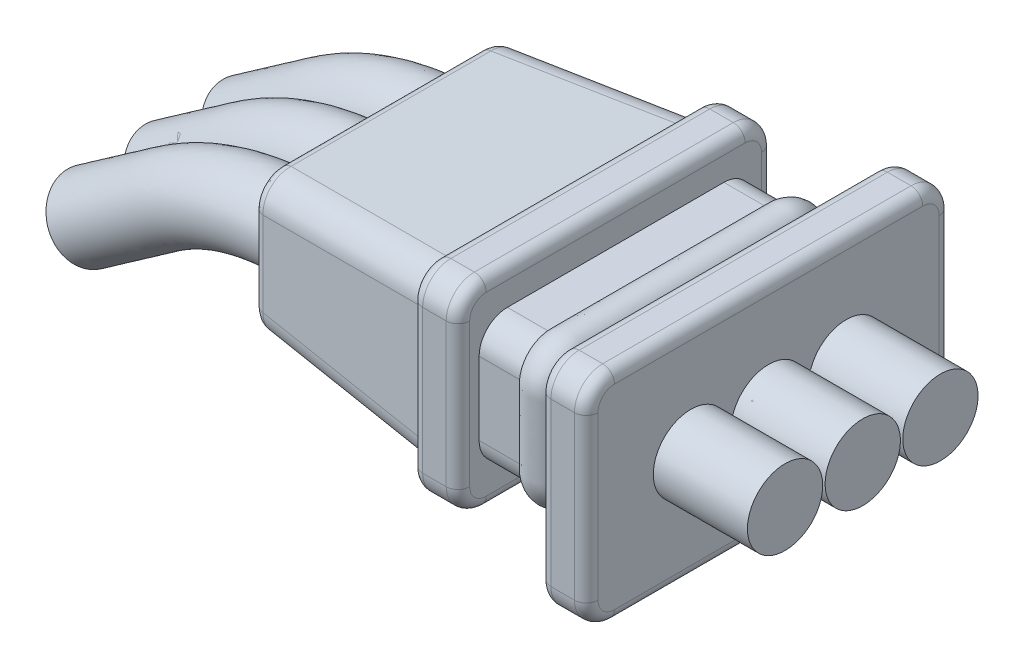
SolidWorks part; units mm, degrees
material "Rubber"
ref_plane "Front Plane" through (0, 0, 0) normal (0, 0, 1) x (1, 0, 0)
ref_plane "Top Plane" through (0, 0, 0) normal (0, 1, 0) x (1, 0, 0)
ref_plane "Right Plane" through (0, 0, 0) normal (1, 0, 0) x (0, 0, -1)
sketch "Sketch1" plane through (0, 0, 0) normal (1, 0, 0) x (0, 0, -1)
  line L1 (-3.875, 2.325) -> (3.875, 2.325)
  line L2 (-3.875, 2.325) -> (-3.875, -2.325)
  line L3 (-3.875, -2.325) -> (3.875, -2.325)
  line L4 (3.875, 2.325) -> (3.875, -2.325)
  line L5 (-3.875, 2.325) -> (3.875, -2.325) construction
  line L6 (-3.875, -2.325) -> (3.875, 2.325) construction
  point P0 (0, 0)
  dimension "D1" = 7.75
  dimension "D2" = 4.65
extrude "Boss-Extrude1" add sketch "Sketch1" along normal blind 1
sketch "Sketch2" plane through (0, 0, 0) normal (-1, 0, 0) x (0, 0, 1)
  line L1 (2.9, -1.375) -> (-2.9, -1.375)
  line L2 (2.9, -1.375) -> (2.9, 1.375)
  line L3 (2.9, 1.375) -> (-2.9, 1.375)
  line L4 (-2.9, -1.375) -> (-2.9, 1.375)
  line L5 (2.9, -1.375) -> (-2.9, 1.375) construction
  line L6 (2.9, 1.375) -> (-2.9, -1.375) construction
  point P0 (0, 0)
  dimension "D1" = 5.8
  dimension "D2" = 2.75
extrude "Boss-Extrude2" add sketch "Sketch2" along normal blind 2.25
sketch "Sketch3" plane through (-2.25, 0, 0) normal (-1, 0, 0) x (0, 0, 1)
  line L1 (3.35, -2.125) -> (-3.35, -2.125)
  line L2 (3.35, -2.125) -> (3.35, 2.125)
  line L3 (3.35, 2.125) -> (-3.35, 2.125)
  line L4 (-3.35, -2.125) -> (-3.35, 2.125)
  line L5 (3.35, -2.125) -> (-3.35, 2.125) construction
  line L6 (3.35, 2.125) -> (-3.35, -2.125) construction
  point P0 (0, 0)
  dimension "D1" = 6.7
  dimension "D2" = 4.25
extrude "Boss-Extrude3" add sketch "Sketch3" along normal blind 1
sketch "Sketch4" plane through (-3.25, 0, 0) normal (-1, 0, 0) x (0, 0, 1)
  line L1 (3.05, -1.825) -> (-3.05, -1.825)
  line L2 (3.05, -1.825) -> (3.05, 1.825)
  line L3 (3.05, 1.825) -> (-3.05, 1.825)
  line L4 (-3.05, -1.825) -> (-3.05, 1.825)
  line L5 (3.05, -1.825) -> (-3.05, 1.825) construction
  line L6 (3.05, 1.825) -> (-3.05, -1.825) construction
  point P0 (0, 0)
  dimension "D1" = 6.1
  dimension "D2" = 3.65
extrude "Boss-Extrude4" add sketch "Sketch4" along normal blind 4 draft 5
fillet "Fillet1" radius 0.6 16 edges at (-1.125, -1.375, -2.9) (-1.125, 1.375, -2.9) (-1.125, -1.375, 2.9) (0.5, 2.325, -3.875) (0.5, -2.325, -3.875) (0.5, -2.325, 3.875) (-2.75, 2.125, -3.35) (-2.75, -2.125, -3.35) (-5.25, -1.65, -2.875) (-5.25, -1.65, 2.875) (-5.25, 1.65, -2.875) (-2.75, -2.125, 3.35) (0.5, 2.325, 3.875) (-1.125, 1.375, 2.9) (-5.25, 1.65, 2.875) (-2.75, 2.125, 3.35)
sketch "Sketch7" plane through (0, 0, 0) normal (-1, 0, 0) x (0, 0, 1)
  line L0 (-2.3, -1.375) -> (2.3, -1.375) construction
  line L1 (-2.9, 0.775) -> (-2.9, -0.775) construction
  line L2 (2.9, -0.775) -> (2.9, 0.775) construction
  line L3 (2.3, 1.375) -> (-2.3, 1.375) construction
  line L4 (-2.3, -1.375) -> (2.3, -1.375)
  line L5 (-2.9, 0.775) -> (-2.9, -0.775)
  line L6 (2.9, -0.775) -> (2.9, 0.775)
  line L7 (2.3, 1.375) -> (-2.3, 1.375)
  arc A0 (-2.9, -0.775) -> (-2.3, -1.375) centre (-2.3, -0.775) ccw construction
  arc A1 (-2.3, 1.375) -> (-2.9, 0.775) centre (-2.3, 0.775) ccw construction
  arc A2 (2.3, -1.375) -> (2.9, -0.775) centre (2.3, -0.775) ccw construction
  arc A3 (2.9, 0.775) -> (2.3, 1.375) centre (2.3, 0.775) ccw construction
  arc A4 (-2.9, -0.775) -> (-2.3, -1.375) centre (-2.3, -0.775) ccw
  arc A5 (-2.3, 1.375) -> (-2.9, 0.775) centre (-2.3, 0.775) ccw
  arc A6 (2.3, -1.375) -> (2.9, -0.775) centre (2.3, -0.775) ccw
  arc A7 (2.9, 0.775) -> (2.3, 1.375) centre (2.3, 0.775) ccw
sketch "Sketch5" plane through (0, 0, 0) normal (0, 1, 0) x (1, 0, 0)
  line L1 (-0.625, 2.9) -> (-1, 2.6835) construction
  line L3 (-1, 2.6835) -> (-1.375, 2.9) construction
  line L5 (-2.25, 2.9) -> (0, 2.9) construction
  line L6 (-2.25, -2.75) -> (-2.25, 2.75) construction
  line L7 (-0.625, 2.9) -> (-1.375, 2.9)
  arc A0 (-1.375, 2.9) -> (-0.625, 2.9) centre (-1, 2.6835) cw
  dimension "D1" = 0.75
  dimension "D2" = 0.875
  dimension "D3" = 120
sweep "Sweep2" add profiles "Sketch5" path "Sketch7"
fillet "Fillet2" radius 0.25 40 edges at (1, -2.1493, 3.6993) (1, 0, 3.875) (1, 2.1493, 3.6993) (1, 2.325, 0) (1, 2.1493, -3.6993) (1, 0, -3.875) (1, -2.1493, -3.6993) (0, -2.1493, 3.6993) (0, 0, 3.875) (0, 2.1493, 3.6993) (0, 2.325, 0) (0, 2.1493, -3.6993) (0, 0, -3.875) (0, -2.1493, -3.6993) (1, -2.325, 0) (0, -2.325, 0) (-7.25, -1.3003, -2.5253) (-7.25, 0, -2.7) (-7.25, 1.3003, -2.5253) (-7.25, 1.475, 0) (-7.25, 1.3003, 2.5253) (-7.25, 0, 2.7) (-7.25, -1.3003, 2.5253) (-3.25, -1.9493, -3.1743) (-3.25, 0, -3.35) (-3.25, 1.9493, -3.1743) (-3.25, 2.125, 0) (-3.25, 1.9493, 3.1743) (-3.25, 0, 3.35) (-3.25, -1.9493, 3.1743) (-2.25, -1.9493, -3.1743) (-2.25, 0, -3.35) (-2.25, 1.9493, -3.1743) (-2.25, 2.125, 0) (-2.25, 1.9493, 3.1743) (-2.25, 0, 3.35) (-2.25, -1.9493, 3.1743) (-7.25, -1.475, 0) (-3.25, -2.125, 0) (-2.25, -2.125, 0)
sketch "Sketch15" plane through (-7.25, 0, 0) normal (-1, 0, 0) x (0, 0, 1)
  line L0 (0, 0) -> (1.65, 0) construction
  line L1 (0, 0) -> (-1.65, 0) construction
  line L2 (-0.8547, 0.25) -> (-0.7953, 0.25)
  line L3 (-0.8547, -0.25) -> (-0.7953, -0.25)
  line L4 (0.7953, -0.25) -> (0.8547, -0.25)
  line L5 (0.7953, 0.25) -> (0.8547, 0.25)
  arc A0 (0.7485, 0.2824) -> (-0.7485, 0.2824) centre (0, 0) ccw
  arc A1 (0.9015, -0.2824) -> (0.9015, 0.2824) centre (1.65, 0) ccw
  arc A2 (-0.9015, 0.2824) -> (-0.9015, -0.2824) centre (-1.65, 0) ccw
  arc A3 (-0.7485, -0.2824) -> (0.7485, -0.2824) centre (0, 0) ccw
  arc A4 (0.8547, -0.25) -> (0.9015, -0.2824) centre (0.8547, -0.3) cw
  arc A5 (0.7485, -0.2824) -> (0.7953, -0.25) centre (0.7953, -0.3) cw
  arc A6 (0.7485, 0.2824) -> (0.7953, 0.25) centre (0.7953, 0.3) ccw
  arc A7 (0.8547, 0.25) -> (0.9015, 0.2824) centre (0.8547, 0.3) ccw
  arc A8 (-0.7953, -0.25) -> (-0.7485, -0.2824) centre (-0.7953, -0.3) cw
  arc A9 (-0.8547, -0.25) -> (-0.9015, -0.2824) centre (-0.8547, -0.3) ccw
  arc A10 (-0.7953, 0.25) -> (-0.7485, 0.2824) centre (-0.7953, 0.3) ccw
  arc A11 (-0.8547, 0.25) -> (-0.9015, 0.2824) centre (-0.8547, 0.3) cw
  point P20 (0.7599, -0.25)
  point P23 (0.7599, 0.25)
  point P28 (-0.7599, -0.25)
  dimension "D1" = 1.6
  dimension "D7" = 0.05
  dimension "D3" = 1.65
  dimension "D5" = 1.65
  dimension "D6" = 0.5
  dimension "D2" = 2
  dimension "D4" = 2
extrude "Cut-Extrude6" cut sketch "Sketch15" against normal through all
sketch "Sketch10" plane through (0, 0, 0) normal (0, 0, 1) x (1, 0, 0)
  line L0 (1, 0) -> (-7.2735, 0)
  line L1 (1, 1.725) -> (1, -1.725) construction
  line L2 (-7.25, -0.8973) -> (-7.25, 0.8973) construction
  line L3 (-10.1414, -0.9042) -> (-11.7797, -2.0514)
  line L4 (1, 0) -> (3, 0)
  arc A0 (-7.2735, 0) -> (-10.1414, -0.9042) centre (-7.2735, -5) ccw
  point P10 (-8.85, 0)
  dimension "D3" = 5
  dimension "D1" = 1.6
  dimension "D2" = 145
  dimension "D4" = 2
  dimension "D5" = 2
sweep "Sweep3" add path "Sketch10" circular profile diameter 1.6 parameters "D3"=1.6
pattern_linear "LPattern1" count 2 spacing 1.65 along (0, 0, -1) count 2 spacing 1.65 along (0, 0, 1) of "Sweep3"
